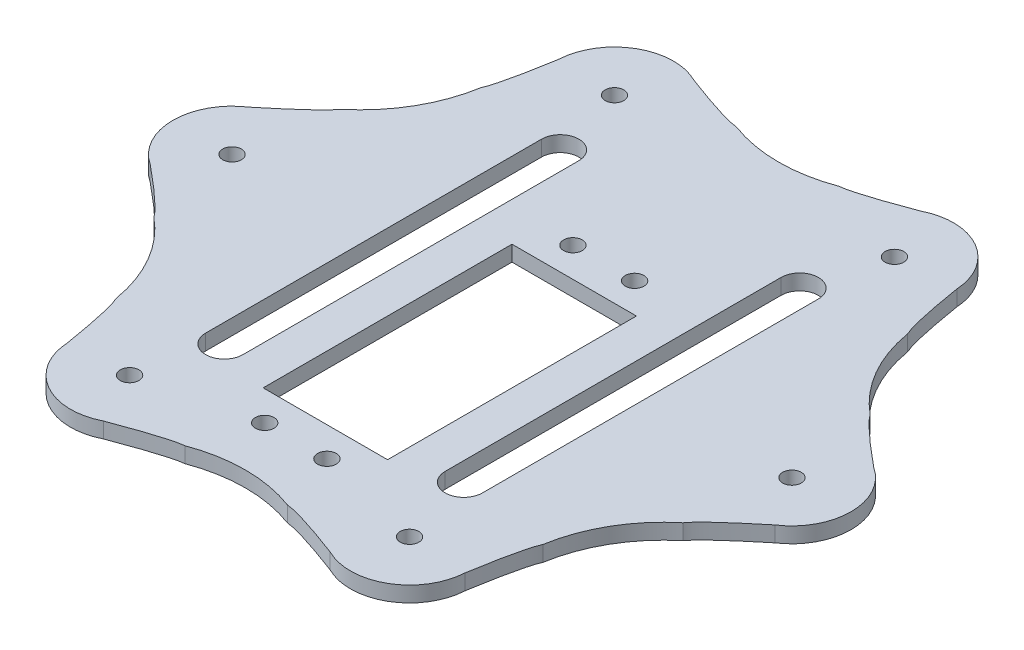
SolidWorks part; units mm, degrees
material "ABS"
ref_plane "Front" through (0, 0, 0) normal (0, 0, 1) x (1, 0, 0)
ref_plane "Top" through (0, 0, 0) normal (0, 1, 0) x (1, 0, 0)
ref_plane "Right" through (0, 0, 0) normal (1, 0, 0) x (0, 0, -1)
sketch "Sketch1" plane through (0, 0, 0) normal (0, 1, 0) x (1, 0, 0)
  line L0 (0, 45) -> (0, -45) construction
  line L1 (-45, 0) -> (45, 0) construction
  line L2 (-10, -30) -> (-10, 0)
  line L3 (10, -30) -> (10, 0)
  line L4 (-10, 0) -> (-10, 10)
  line L5 (-10, -30) -> (10, -30)
  line L6 (-22.25, 27) -> (-22.25, -27)
  line L7 (-16.25, 27) -> (-16.25, -27)
  line L8 (16.25, 27) -> (16.25, -27)
  line L9 (22.25, 27) -> (22.25, -27)
  line L10 (0, 45) -> (0, 37.5) construction
  line L11 (10, 0) -> (10, 10)
  line L12 (-10, 10) -> (10, 10)
  line L16 (-4.955, 14.75) -> (-5, -34.75) construction
  line L18 (0, 6.1303) -> (0, -27.7397) construction
  circle A0 centre (0, 0) radius 45
  arc A1 (-22.25, 27) -> (-16.25, 27) centre (-19.25, 27) cw
  arc A2 (-22.25, -27) -> (-16.25, -27) centre (-19.25, -27) ccw
  arc A3 (22.25, -27) -> (16.25, -27) centre (19.25, -27) cw
  arc A4 (22.25, 27) -> (16.25, 27) centre (19.25, 27) ccw
  circle A5 centre (-5, -34.75) radius 1.5
  circle A6 centre (5, -34.75) radius 1.5
  circle A7 centre (-4.955, 14.75) radius 1.5
  circle A8 centre (4.955, 14.75) radius 1.5
  point P11 (0, 24.3484)
  point P13 (10, 0)
  point P14 (-10, 0)
  point P18 (-22.25, 0)
  point P28 (22.25, 0)
  point P30 (0, 0)
  point P40 (0, 0)
  point P41 (0, 0)
  dimension "D3" = 3
  dimension "D5" = 9.91
  dimension "D6" = 90
  dimension "D7" = 20
  dimension "D9" = 10
  dimension "D10" = 3
  dimension "D1" = 30
  dimension "D2" = 10
  dimension "D4" = 49.5
  dimension "D8" = 34.75
  dimension "D11" = 19.25
  dimension "D12" = 24.3484
extrude "Boss-Extrude2" add sketch "Sketch1" along normal blind 2.5
ref_plane "Plane1" through (0, 2.5, 0) normal (0, 1, 0) x (1, 0, 0)
sketch "Sketch2" plane through (0, 2.5, 0) normal (0, 1, 0) x (1, 0, 0)
  line L0 (0, 45) -> (0, -45) construction
  line L1 (-45, 0) -> (45, 0) construction
  line L2 (-54.5, 0) -> (-35.5, 0) construction
  line L4 (-51.7175, -6.7175) -> (-45, 0) construction
  circle A0 centre (0, 0) radius 45 construction
  arc A2 (-42.2345, 15.532) -> (-42.2345, -15.532) centre (0, 0) ccw
  arc A3 (-50.2124, 7.9424) -> (-50.2124, -7.9424) centre (-45, 0) ccw
  spline S0 degree 3 poles (-50.2124, -7.9424) (-45.316, -11.9596) (-42.6567, -14.4895) (-42.2345, -15.532) knots 0.089312 0.089312 0.089312 0.089312 1 1 1 1
  spline S1 degree 3 poles (-50.2124, 7.9424) (-45.316, 11.9596) (-42.6567, 14.4895) (-42.2345, 15.532) knots 0.089312 0.089312 0.089312 0.089312 1 1 1 1
  dimension "D2" = 45
extrude "Boss-Extrude4" add sketch "Sketch2" against normal up to surface (2.5 mm away) up to face at (-19.25, 0, 0)
pattern_circular "CirPattern1" count 6 over 360 about axis through (0, 2.5, 0) along (0, 1, 0) of "Boss-Extrude4"
ref_plane "Plane2" through (0, 2.5, 0) normal (0, 1, 0) x (1, 0, 0)
sketch "Sketch5" plane through (0, 2.5, 0) normal (0, 1, 0) x (1, 0, 0)
  line L0 (0, 45) -> (0, -45) construction
  line L1 (-8.2247, 44.3422) -> (0, 46.6578)
  line L2 (0, 46.6578) -> (8.2247, 44.3422)
  line L3 (40.4069, 23.3289) -> (42.5138, 15.0483)
  line L4 (34.2891, 29.2939) -> (40.4069, 23.3289)
  line L5 (40.4069, -23.3289) -> (34.2891, -29.2939)
  line L6 (42.5138, -15.0483) -> (40.4069, -23.3289)
  line L7 (0, -46.6578) -> (-8.2247, -44.3422)
  line L8 (8.2247, -44.3422) -> (0, -46.6578)
  line L9 (-40.4069, -23.3289) -> (-42.5138, -15.0483)
  line L10 (-34.2891, -29.2939) -> (-40.4069, -23.3289)
  line L11 (-40.4069, 23.3289) -> (-34.2891, 29.2939)
  line L12 (-42.5138, 15.0483) -> (-40.4069, 23.3289)
  arc A0 (7.6662, 44.3422) -> (-7.6662, 44.3422) centre (0, 0) ccw construction
  arc A1 (-7.6662, -44.3422) -> (7.6662, -44.3422) centre (0, 0) ccw construction
  arc A2 (-8.2247, 44.3422) -> (8.2247, 44.3422) centre (0, 66.2885) ccw
  arc A3 (34.2891, 29.2939) -> (42.5138, 15.0483) centre (57.4076, 33.1443) ccw
  arc A4 (42.5138, -15.0483) -> (34.2891, -29.2939) centre (57.4076, -33.1443) ccw
  arc A5 (8.2247, -44.3422) -> (-8.2247, -44.3422) centre (0, -66.2885) ccw
  arc A6 (-34.2891, -29.2939) -> (-42.5138, -15.0483) centre (-57.4076, -33.1443) ccw
  arc A7 (-42.5138, 15.0483) -> (-34.2891, 29.2939) centre (-57.4076, 33.1443) ccw
  parabola Q0 (-7.6662, 44.3422) -> (-18.2279, 47.4564) focus (-7.4049, 44.5798) apex (-7.3043, 44.5299) construction
  parabola Q1 (18.2279, 47.4564) -> (7.6662, 44.3422) focus (7.4049, 44.5798) apex (7.3043, 44.5299) construction
  point P42 (0, 0)
  dimension "D1" = 6
extrude "Cut-Extrude2" cut sketch "Sketch5" against normal blind 2.5
ref_plane "Plane3" through (0, 2.5, 0) normal (0, 1, 0) x (1, 0, 0)
sketch "Sketch6" plane through (0, 2.5, 0) normal (0, 1, 0) x (1, 0, 0)
  line L0 (0, 42.8517) -> (0, -42.8517) construction
  circle A0 centre (-45, 0) radius 1.5
  arc A1 (-8.2247, 44.3422) -> (8.2247, 44.3422) centre (0, 66.2885) ccw construction
  arc A2 (8.2247, -44.3422) -> (-8.2247, -44.3422) centre (0, -66.2885) ccw construction
  circle A7 centre (-22.5, 38.9711) radius 1.5
  circle A8 centre (22.5, 38.9711) radius 1.5
  circle A9 centre (45, 0) radius 1.5
  circle A10 centre (22.5, -38.9711) radius 1.5
  circle A11 centre (-22.5, -38.9711) radius 1.5
  point P37 (0, 0)
  dimension "D4" = 3
  dimension "D5" = 22.5
  dimension "D3" = 6
extrude "Cut-Extrude3" cut sketch "Sketch6" against normal mid plane 10
